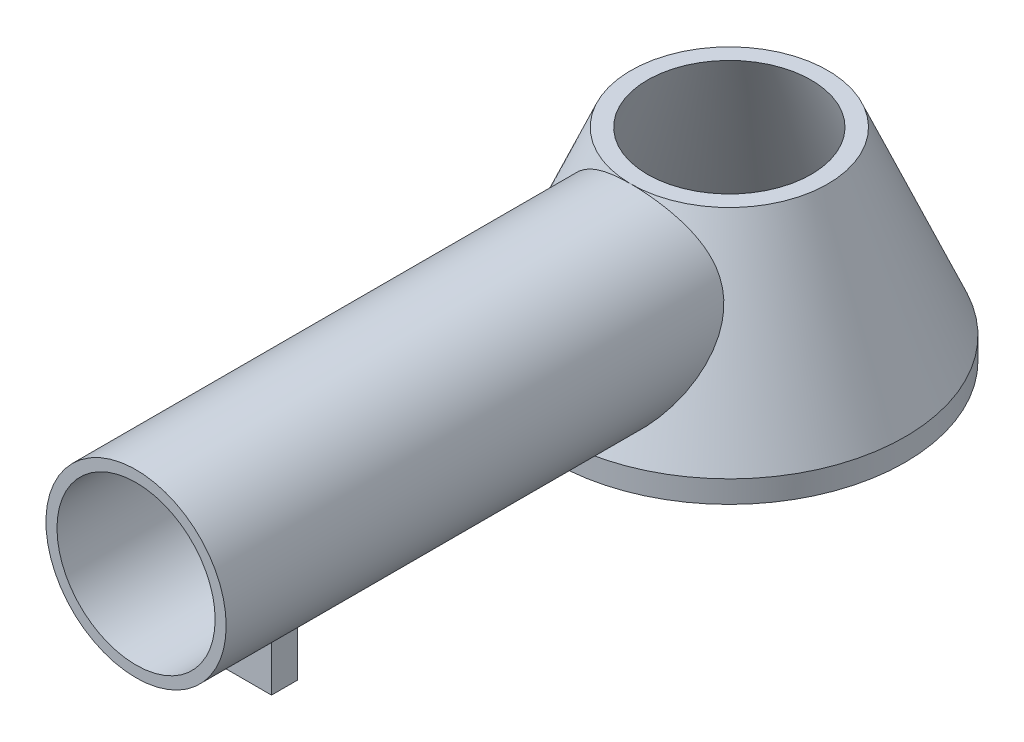
SolidWorks part; units mm, degrees
ref_plane "Front Plane" through (0, 0, 0) normal (0, 0, 1) x (1, 0, 0)
ref_plane "Top Plane" through (0, 0, 0) normal (0, 1, 0) x (1, 0, 0)
ref_plane "Right Plane" through (0, 0, 0) normal (1, 0, 0) x (0, 0, -1)
sketch "Sketch6" plane through (0, 0, 0) normal (0, 0, 1) x (1, 0, 0)
  circle A0 centre (0, 0) radius 8.15
  circle A1 centre (0, 0) radius 7.15
  dimension "D1" = 14.3
  dimension "D2" = 16.3
extrude "Boss-Extrude3" add sketch "Sketch6" along normal blind 46.25 contours A0 | A1
sketch "Sketch7" plane through (0, 0, 0) normal (0, 0, -1) x (-1, 0, 0)
  line L0 (0, 55) -> (0, -55) construction
  circle A0 centre (0, 0) radius 8.15 construction
  point P0 (0, 8.15)
  point P1 (0, -8.15)
ref_plane "Plane4" through (0, 8.15, 0) normal (0, 1, 0) x (1, 0, 0)
ref_plane "Plane5" through (0, -8.15, 0) normal (0, 1, 0) x (1, 0, 0)
sketch "Sketch10" plane through (0, 0, 0) normal (1, 0, 0) x (0, 0, -1)
  line L0 (-8.5, -8.15) -> (-1.5, 8.15)
  line L1 (-1.5, 8.15) -> (0, 8.15)
  line L2 (0, 8.15) -> (-7, -8.15)
  line L3 (-7, -8.15) -> (-8.5, -8.15)
  line L5 (7.4, 14.6337) -> (7.4, -13.5429) construction
  point P2 (-0.75, 8.15)
  dimension "D1" = 1.5
  dimension "D2" = 0
  dimension "D3" = 0
  dimension "D4" = 7.4
  dimension "D5" = 7
  dimension "D6" = 16.3
revolve "Revolve1" add sketch "Sketch10" angle 360 about L5
sketch "Sketch12" plane through (0, -8.15, 0) normal (0, -1, 0) x (1, 0, 0)
  circle A0 centre (0, -7.4) radius 14.4
  circle A1 centre (-0.0014, -7.3988) radius 15.9018
  circle M1 centre (0, -7.4) radius 14.4
  circle M2 centre (0, -7.4) radius 15.9
extrude "Boss-Extrude10" add sketch "Sketch12" along normal blind 2 contours M2 M1
thread "Thread1" pitch 0.25 start angle 0, offset 0, length 2, pitch 0.25, diameter 28.8
ref_plane "Plane6" through (14.4, -10.15, -7.4) normal (0, 0, 1) x (1, 0, 0)
sketch "Thread Profile1" plane through (14.4, -10.15, -7.4) normal (0, 0, 1) x (1, 0, 0)
  line L0 (0, 0) -> (0, 0.25) construction
  line L11 (0, 0) -> (0, 0.2187)
  line L12 (0, 0.2187) -> (-0.1353, 0.1406)
  line L13 (-0.1353, 0.1406) -> (-0.1353, 0.0781)
  line L15 (-0.1353, 0.0781) -> (0, 0)
  line L17 (-0.1353, 0.1094) -> (0, 0.1094) construction
  point P2 (0, 0)
  dimension "Pitch" = 0.25
  dimension "Profile_Angle" = 60
  dimension "Profile_Land" = 0.0625
  dimension "Profile_Height" = 0.1353
sketch "Sketch15" plane through (0, 0, 46.25) normal (0, 0, 1) x (1, 0, 0)
  circle A0 centre (0, 0) radius 7.15
  circle A1 centre (0, 0) radius 7.15 construction
  dimension "D1" = 0
extrude "Cut-Extrude1" cut sketch "Sketch15" against normal blind 60
sketch "Sketch16" plane through (0, -10.15, 0) normal (0, -1, 0) x (1, 0, 0)
  line L1 (-5.4803, 39.4786) -> (5.4775, 39.4786)
  line L2 (-5.4803, 39.4786) -> (-5.4803, 37.1305)
  line L3 (-5.4803, 37.1305) -> (5.4775, 37.1305)
  line L4 (5.4775, 39.4786) -> (5.4775, 37.1305)
extrude "Boss-Extrude11" add sketch "Sketch16" against normal up to surface (4.1151 mm away)
sketch "Sketch17" plane through (0, 0, 0) normal (0, 0, -1) x (-1, 0, 0)
  circle A0 centre (0, 0) radius 7.15
  circle A1 centre (0, 0) radius 7.15 construction
  circle A2 centre (0, 0) radius 6
  dimension "D1" = 0
  dimension "D2" = 12
extrude "Boss-Extrude12" add sketch "Sketch17" against normal blind 1
